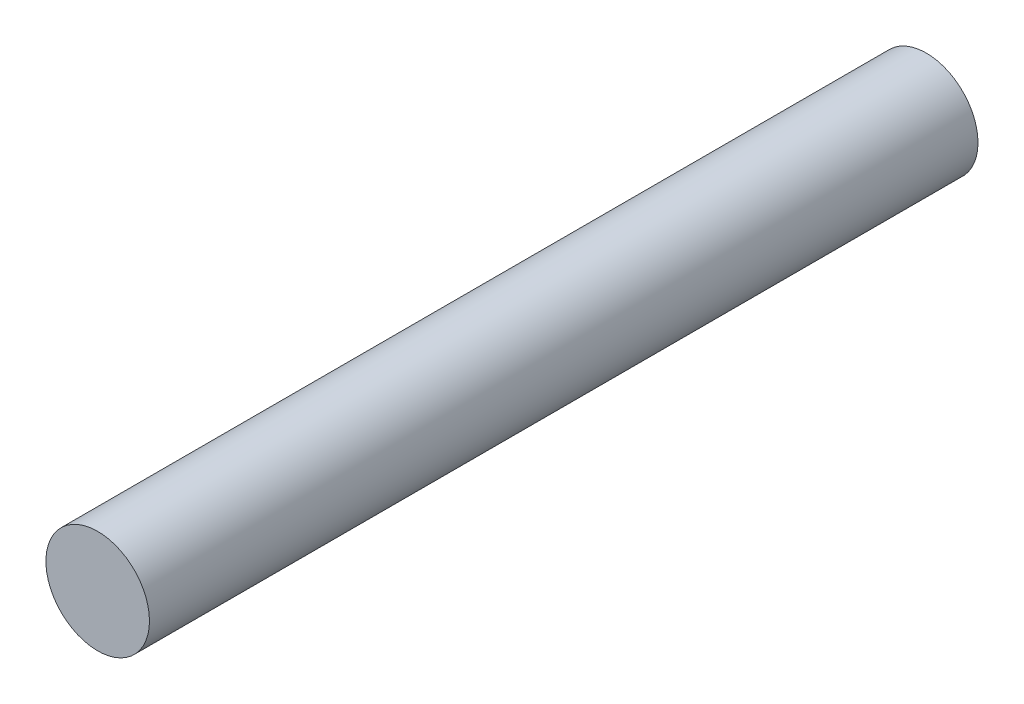
SolidWorks part; units mm, degrees
material "Alloy Steel"
ref_plane "Front Plane" through (0, 0, 0) normal (0, 0, 1) x (1, 0, 0)
ref_plane "Top Plane" through (0, 0, 0) normal (0, 1, 0) x (1, 0, 0)
ref_plane "Right Plane" through (0, 0, 0) normal (1, 0, 0) x (0, 0, -1)
sketch "Sketch1" plane through (0, 0, 0) normal (0, 0, 1) x (1, 0, 0)
  circle A0 centre (0, 0) radius 3
  dimension "D1" = 6
extrude "Boss-Extrude1" add sketch "Sketch1" along normal blind 48
ref_axis "Axis1" through (0, 0, 48) along (0, 0, -1)
